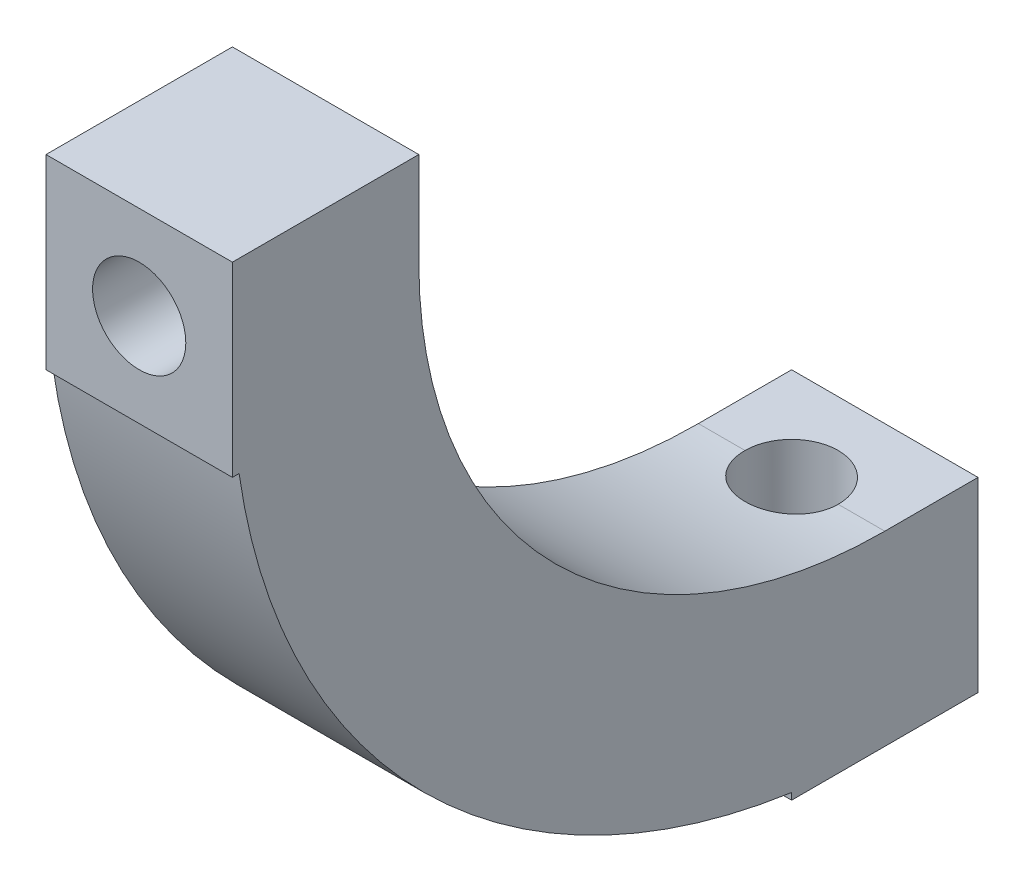
SolidWorks part; units mm, degrees
ref_plane "Front Plane" through (0, 0, 0) normal (0, 0, 1) x (1, 0, 0)
ref_plane "Top Plane" through (0, 0, 0) normal (0, 1, 0) x (1, 0, 0)
ref_plane "Right Plane" through (0, 0, 0) normal (1, 0, 0) x (0, 0, -1)
ref_axis "Z" through (0, 0, 22.75) along (0, 0, -1)
sketch "Sketch4" plane through (0, 0, 0) normal (0, 0, 1) x (1, 0, 0)
  circle A0 centre (0, 0) radius 14 construction
  point P2 (-3.8685, -1.4102)
  dimension "D1" = 28
sketch "Sketch5" plane through (0, 0, 0) normal (1, 0, 0) x (0, 0, -1)
  line L0 (15.4, 0) -> (-15.4, 0) construction
  line L1 (0, 15.4) -> (0, -15.4) construction
  line L2 (-21, 0) -> (-21, 3)
  line L3 (0, -21) -> (3, -21)
  line L4 (0, -15) -> (3, -15)
  line L5 (-15, 0) -> (-15, 3)
  line L6 (-21, 3) -> (-15, 3)
  line L7 (3, -15) -> (3, -21)
  line L8 (-21, 0) -> (-21, -3)
  line L9 (-21, -3) -> (-20.7846, -3)
  line L10 (0, -21) -> (-3, -21)
  line L11 (-3, -21) -> (-3, -20.7846)
  circle A0 centre (0, 0) radius 14 construction
  arc A1 (-3, -20.7846) -> (-20.7846, -3) centre (0, 0) cw
  arc A2 (0, -15) -> (-15, 0) centre (0, 0) cw
  arc A3 (0, -21) -> (-3, -20.7846) centre (0, 0) cw construction
  arc A4 (-20.7846, -3) -> (-21, 0) centre (0, 0) cw construction
  arc A5 (0, -21) -> (-21, 0) centre (0, 0) cw construction
  point P17 (0, 0)
  point P21 (-12.6663, -14.1621)
  dimension "D1" = 28
  dimension "D3" = 15
  dimension "D4" = 3
  dimension "D2" = 6
sketch "Sketch6" plane through (0, 0, 0) normal (0, 1, 0) x (1, 0, 0)
  circle A0 centre (0, 0) radius 14 construction
  dimension "D1" = 28
extrude "Boss-Extrude1" add sketch "Sketch5" along normal blind 3 and the other way blind 3
sketch "Sketch7" plane through (0, 0, 0) normal (0, 0, 1) x (1, 0, 0)
  circle A0 centre (0, 0) radius 1.5
  dimension "D1" = 3
extrude "Cut-Extrude1" cut sketch "Sketch7" along normal through all
sketch "Sketch8" plane through (0, 0, 0) normal (0, 1, 0) x (1, 0, 0)
  circle A0 centre (0, 0) radius 1.5
  dimension "D1" = 3
extrude "Cut-Extrude2" cut sketch "Sketch8" against normal through all
ref_axis "Y" through (0, -9.3489, 0) along (0, -1, 0)
equation "\"rbracket-width\" = \"L2Thickness\""
equation "\"EyeCaptureRadius\"= ( \"EyeDiameter\" + \"EyeClearance\" ) / 2"
equation "\"rbracket_planetocenterline_dist\"= \"BasePlaneDistance\""
equation "\"EyeDiameter\" = 28"
equation "\"BasePlaneDistance\" = 45"
equation "\"EyeClearance\" = 2"
equation "\"D1@Sketch4\"=\"EyeDiameter\""
equation "\"D1@Sketch6\"=\"EyeDiameter\""
equation "\"D2@Sketch5\"=\"rbracket-width\""
equation "\"D3@Sketch5\"=(\"EyeDiameter\"+\"EyeClearance\")/2"
equation "\"D1@Boss-Extrude1\"=\"rbracket-width\"/2"
equation "\"D2@Boss-Extrude1\"=\"rbracket-width\"/2"
equation "\"L2Thickness\" = 6"
